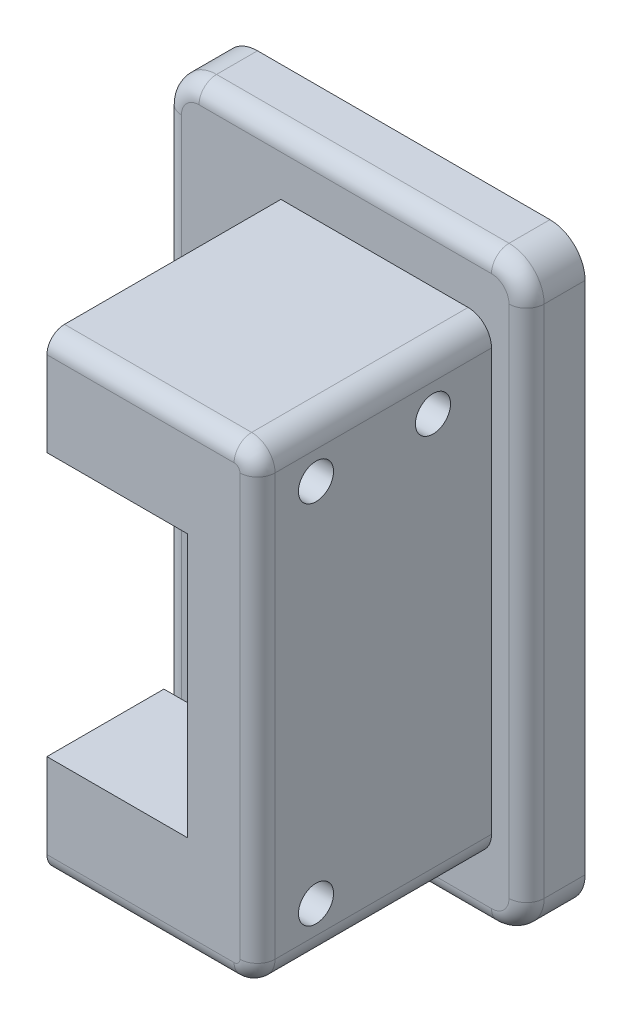
SolidWorks part; units mm, degrees
ref_plane "Front Plane" through (0, 0, 0) normal (0, 0, 1) x (1, 0, 0)
ref_plane "Top Plane" through (0, 0, 0) normal (0, 1, 0) x (1, 0, 0)
ref_plane "Right Plane" through (0, 0, 0) normal (1, 0, 0) x (0, 0, -1)
sketch "Sketch1" plane through (0, 0, 0) normal (0, 0, 1) x (1, 0, 0)
  line L0 (-130, -28) -> (-148, -28)
  line L1 (-148, -28) -> (-148, -36.75)
  line L2 (-148, -68) -> (-130, -68)
  line L3 (-148, -59.25) -> (-148, -68)
  line L4 (-148, -36.75) -> (-136, -36.75)
  line L6 (-148, -59.25) -> (-136, -59.25)
  line L7 (-136, -36.75) -> (-136, -59.25)
  line L8 (-130, -28) -> (-130, -68)
  dimension "D1" = 40
  dimension "D2" = 6
  dimension "D3" = 22.5
  dimension "D4" = 8.75
  dimension "D5" = 12
extrude "Boss-Extrude1" add sketch "Sketch1" against normal blind 20
sketch "Sketch2" plane through (0, 0, 0) normal (0, 0, 1) x (1, 0, 0)
  line L7 (-130, -28) -> (-148, -28)
  line L8 (-130, -28) -> (-148, -28)
  line L9 (-148, -28) -> (-148, -36.75)
  line L10 (-148, -28) -> (-148, -36.75)
  line L11 (-148, -36.75) -> (-136, -36.75)
  line L12 (-148, -36.75) -> (-136, -36.75)
  line L13 (-136, -36.75) -> (-136, -59.25)
  line L14 (-136, -36.75) -> (-136, -59.25)
  line L15 (-136, -59.25) -> (-148, -59.25)
  line L16 (-136, -59.25) -> (-148, -59.25)
  line L17 (-148, -59.25) -> (-148, -68)
  line L18 (-148, -59.25) -> (-148, -68)
  line L19 (-148, -68) -> (-130, -68)
  line L20 (-148, -68) -> (-130, -68)
  line L22 (-130, -68) -> (-130, -28)
  line L23 (-130, -68) -> (-130, -28)
  dimension "D1" = 0
sketch "Sketch3" plane through (0, 0, -20) normal (0, 0, -1) x (-1, 0, 0)
  line L0 (148, -68) -> (130, -68) construction
  line L1 (155, -73) -> (130, -73)
  line L2 (158, -70) -> (158, -26)
  line L3 (155, -23) -> (130, -23)
  line L4 (127, -70) -> (127, -26)
  line L5 (130, -28) -> (148, -28) construction
  line L6 (148, -28) -> (148, -36.75) construction
  line L7 (130, -68) -> (130, -28) construction
  arc A0 (155, -73) -> (158, -70) centre (155, -70) ccw
  arc A1 (130, -73) -> (127, -70) centre (130, -70) cw
  arc A2 (130, -23) -> (127, -26) centre (130, -26) ccw
  arc A3 (158, -26) -> (155, -23) centre (155, -26) ccw
  dimension "D5" = 3
  dimension "D1" = 5
  dimension "D2" = 5
  dimension "D3" = 10
  dimension "D4" = 3
extrude "Boss-Extrude2" add sketch "Sketch3" along normal blind 5
fillet "Fillet1" radius 2 2 edges at (-130, -28, -10) (-130, -68, -10)
sketch "Sketch4" plane through (0, -68, 0) normal (0, -1, 0) x (1, 0, 0)
  line L1 (-148, -20) -> (-138, -20)
  line L2 (-148, -20) -> (-148, -10)
  line L3 (-148, -10) -> (-138, -10)
  line L4 (-138, -20) -> (-138, -10)
  dimension "D1" = 10
  dimension "D2" = 10
extrude "Cut-Extrude1" cut sketch "Sketch4" against normal up to surface (8.75 mm away) up to face at (-142, -59.25, -10)
sketch "Sketch5" plane through (-148, 0, 0) normal (-1, 0, 0) x (0, 0, 1)
  line L2 (-20, -48) -> (0, -48) construction
  line L3 (-20, -70) -> (-20, -26) construction
  line L4 (0, -36.75) -> (0, -59.25) construction
  circle A0 centre (-5, -32.375) radius 1.5
  circle A1 centre (-15, -32.375) radius 1.5
  circle A3 centre (-5, -63.625) radius 1.5
extrude "Cut-Extrude2" cut sketch "Sketch5" against normal through all
fillet "Fillet2" radius 1.5 13 edges at (-140, -68, 0) (-130.5858, -67.4142, 0) (-130, -48, 0) (-140, -28, 0) (-157.1213, -23.8787, -20) (-158, -48, -20) (-157.1213, -72.1213, -20) (-142.5, -73, -20) (-127.8787, -72.1213, -20) (-127, -48, -20) (-127.8787, -23.8787, -20) (-130.5858, -28.5858, 0) (-142.5, -23, -20)
